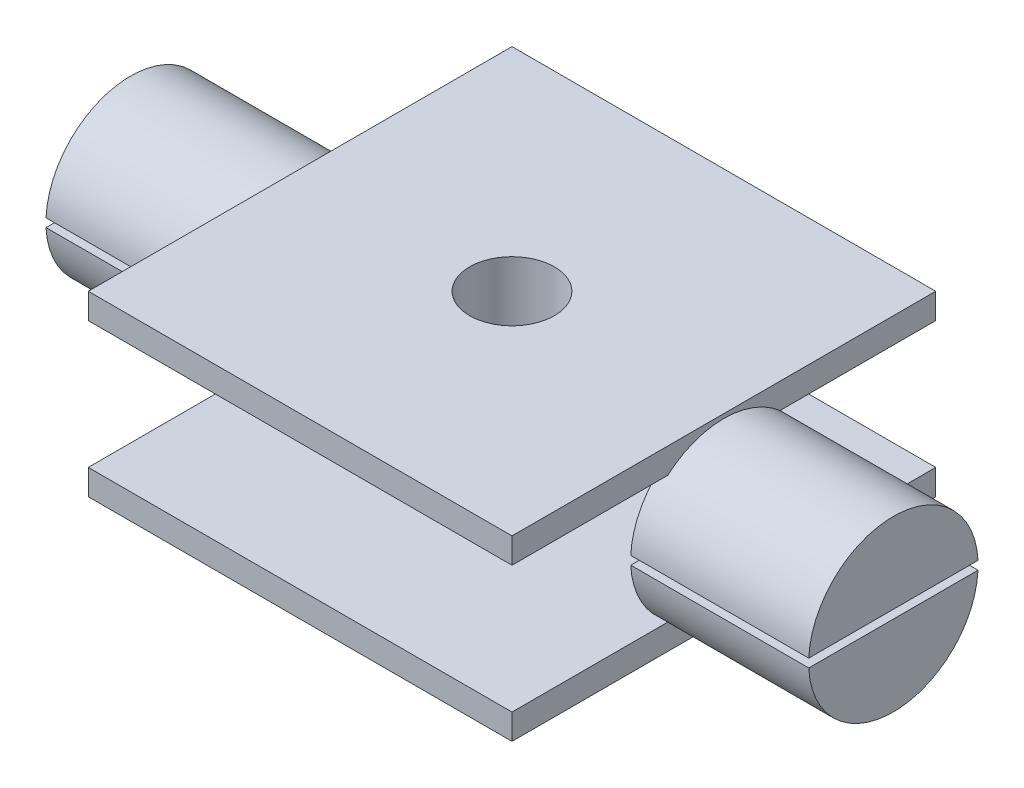
SolidWorks part; units mm, degrees
note: '?' marks a value the reader was unsure of.
ref_plane "Front Plane" through (0, 0, 0) normal (0, 0, 1) x (1, 0, 0)
ref_plane "Top Plane" through (0, 0, 0) normal (0, 1, 0) x (1, 0, 0)
ref_plane "Right Plane" through (0, 0, 0) normal (1, 0, 0) x (0, 0, -1)
sketch "Sketch1" plane through (0, 0, 0) normal (0, 1, 0) x (1, 0, 0)
  circle A0 centre (0, 0) radius 10
  dimension "D1" = 20
extrude "Boss-Extrude1" add sketch "Sketch1" along normal blind 15
sketch "Sketch3" plane through (0, 0, 0) normal (0, -1, 0) x (1, 0, 0)
  line L1 (-25, -25) -> (25, -25)
  line L2 (-25, -25) -> (-25, 25)
  line L3 (-25, 25) -> (25, 25)
  line L4 (25, -25) -> (25, 25)
  line L5 (-25, -25) -> (25, 25) construction
  line L6 (-25, 25) -> (25, -25) construction
  point P0 (0, 0)
  dimension "D1" = 50
  dimension "D2" = 50
extrude "Boss-Extrude2" add sketch "Sketch3" along normal blind 3
sketch "Sketch5" plane through (0, 15, 0) normal (0, 1, 0) x (1, 0, 0)
  line L1 (-25, -25) -> (25, -25)
  line L2 (-25, -25) -> (-25, 25)
  line L3 (-25, 25) -> (25, 25)
  line L4 (25, -25) -> (25, 25)
  line L5 (-25, -25) -> (25, 25) construction
  line L6 (-25, 25) -> (25, -25) construction
  point P0 (0, 0)
  dimension "D1" = 50
  dimension "D2" = 50
extrude "Boss-Extrude4" add sketch "Sketch5" along normal blind 3
sketch "Sketch6" plane through (0, 18, 0) normal (0, 1, 0) x (1, 0, 0)
  circle A0 centre (0, 0) radius 5
  dimension "D1" = 10
ref_axis "Axis1" through (-25, -3, 0) along (0, 1, 0)?
ref_axis "Axis2" through (25, 18, 0) along (0, -1, 0)?
sketch "Sketch7" plane through (-25, 0, 0) normal (-1, 0, 0) x (0, 0, 1)
  line L1 (0, 0) -> (0, 15)
  line L2 (-25, 15) -> (25, 15) construction
  circle A1 centre (0, 7.5) radius 10
  dimension "D1" = 20
extrude "Boss-Extrude5" add sketch "Sketch7" along normal blind 20 and the other way blind 1 contours A1
sketch "Sketch8" plane through (25, 0, 0) normal (1, 0, 0) x (0, 0, -1)
  line L0 (0, 0) -> (0, 15)
  line L1 (25, 0) -> (-25, 0) construction
  line L2 (-25, 15) -> (25, 15) construction
  circle A0 centre (0, 7.5) radius 10
  dimension "D1" = 20
extrude "Boss-Extrude6" add sketch "Sketch8" along normal blind 20 and the other way blind 1 contours A0
sketch "Sketch9" plane through (-45, 0, 0) normal (-1, 0, 0) x (0, 0, 1)
  line L1 (-14.4828, 7) -> (14.4828, 7)
  line L2 (-14.4828, 7) -> (-14.4828, 8)
  line L3 (-14.4828, 8) -> (14.4828, 8)
  line L4 (14.4828, 7) -> (14.4828, 8)
  line L5 (-14.4828, 7) -> (14.4828, 8) construction
  line L6 (-14.4828, 8) -> (14.4828, 7) construction
  point P0 (0, 7.5)
  dimension "D1" = 1
extrude "Cut-Extrude2" cut sketch "Sketch9" against normal up to surface (21 mm away) up to face at (-24, 7.5, 0)
sketch "Sketch10" plane through (45, 0, 0) normal (1, 0, 0) x (0, 0, -1)
  line L1 (-17.3427, 8) -> (17.3427, 8)
  line L2 (-17.3427, 8) -> (-17.3427, 7)
  line L3 (-17.3427, 7) -> (17.3427, 7)
  line L4 (17.3427, 8) -> (17.3427, 7)
  line L5 (-17.3427, 8) -> (17.3427, 7) construction
  line L6 (-17.3427, 7) -> (17.3427, 8) construction
  point P0 (0, 7.5)
  dimension "D1" = 1
extrude "Cut-Extrude3" cut sketch "Sketch10" against normal up to surface (21 mm away) up to face at (24, 7.5, 0)
extrude "Cut-Extrude4" cut sketch "Sketch6" against normal through all
sketch "Sketch11" plane through (-45, 0, 0) normal (-1, 0, 0) x (0, 0, 1)
  circle A0 centre (0, 7.5) radius 8
  arc A2 (-9.9875, 7) -> (9.9875, 7) centre (0, 7.5) ccw construction
  dimension "D1" = 2
extrude "Cut-Extrude5" cut sketch "Sketch11" against normal offset from surface (17 mm away) 2 from offset 2 up to face at (-24, 3.3295, 0) offset against normal yes
other "SurfaceCut1" flip cut yes
mirror "Mirror2" about plane through (0, 0, 0) normal (1, 0, 0) of bodies 113
